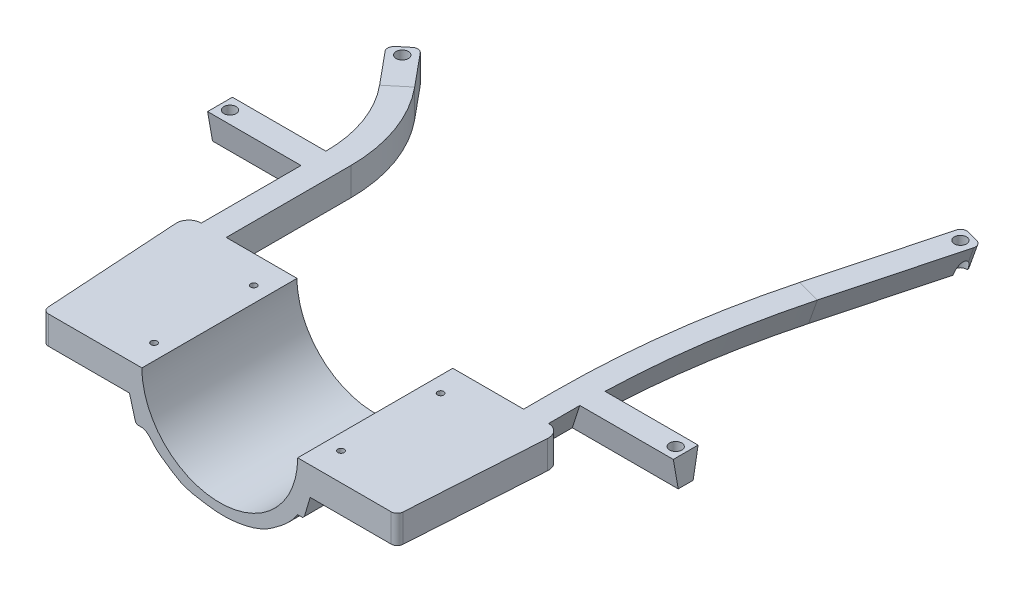
SolidWorks part; units mm, degrees
ref_plane "Front Plane" through (0, 0, 0) normal (0, 0, 1) x (1, 0, 0)
ref_plane "Top Plane" through (0, 0, 0) normal (0, 1, 0) x (1, 0, 0)
ref_plane "Right Plane" through (0, 0, 0) normal (1, 0, 0) x (0, 0, -1)
sketch "Sketch1" plane through (0, 0, 0) normal (0, 1, 0) x (1, 0, 0)
  line L1 (-38.1, 15.8115) -> (38.1, 15.8115)
  line L2 (-38.1, 15.8115) -> (-38.1, -15.8115)
  line L3 (-38.1, -15.8115) -> (38.1, -15.8115)
  line L4 (38.1, 15.8115) -> (38.1, -15.8115)
  line L5 (-38.1, 15.8115) -> (38.1, -15.8115) construction
  line L6 (-38.1, -15.8115) -> (38.1, 15.8115) construction
  point P0 (0, 0)
  dimension "D1" = 76.2
  dimension "D2" = 31.623
extrude "Boss-Extrude1" add sketch "Sketch1" along normal blind 5.715
sketch "Sketch2" plane through (0, 5.715, 0) normal (0, 1, 0) x (1, 0, 0)
  line L0 (-38.1, 15.8115) -> (-38.1, -15.8115)
  line L1 (-38.1, -15.8115) -> (-36.1, -15.8115)
  line L2 (-38.1, -15.8115) -> (38.1, -15.8115) construction
  line L3 (-36.1, -15.8115) -> (-38.1, 15.8115)
  dimension "D1" = 2
extrude "Cut-Extrude1" cut sketch "Sketch2" against normal blind 5.715
mirror "Mirror1" about plane through (0, 0, 0) normal (1, 0, 0) of "Cut-Extrude1"
fillet "Fillet1" radius 2.54 2 edges at (38.1, 2.8575, -15.8115) (-38.1, 2.8575, -15.8115)
fillet "Fillet2" radius 1.27 2 edges at (36.1, 2.8575, 15.8115) (-36.1, 2.8575, 15.8115)
sketch "Sketch3" plane through (0, 5.715, 0) normal (0, 1, 0) x (1, 0, 0)
  line L0 (-15.875, 15.8115) -> (-15.875, -15.8115) construction
  line L2 (35.3943, 15.8115) -> (-35.3943, 15.8115) construction
  line L3 (-34.9078, -15.8115) -> (34.9078, -15.8115) construction
  line L4 (-15.875, -15.8115) -> (15.875, -15.8115) construction
  line L5 (15.875, -15.8115) -> (15.875, 15.8115) construction
  line L6 (15.875, 15.8115) -> (-15.875, 15.8115) construction
  line L8 (15.875, 15.8115) -> (-15.875, 15.8115)
  line L9 (15.875, 15.8115) -> (15.875, -15.8115)
  line L10 (15.875, -15.8115) -> (-15.875, -15.8115)
  line L11 (-15.875, 15.8115) -> (-15.875, -15.8115)
  line L12 (15.875, 15.8115) -> (-15.875, -15.8115) construction
  line L13 (15.875, -15.8115) -> (-15.875, 15.8115) construction
  point P7 (0, 0)
  dimension "D1" = 31.75
  dimension "D2" = 15.875
extrude "Cut-Extrude2" cut sketch "Sketch3" against normal blind 5.715
sketch "Sketch4" plane through (0, 0, 0) normal (0, 0, 1) x (1, 0, 0)
  line L0 (-15.875, 0) -> (-18.415, 0)
  line L1 (-18.415, 0) -> (-17.0978, -4.8055)
  line L2 (17.145, -4.318) -> (15.8423, -4.318)
  line L3 (-17.0978, -4.8055) -> (-15.875, -4.8055)
  line L4 (15.875, 0) -> (18.415, 0)
  line L5 (15.875, 0) -> (34.9078, 0) construction
  line L6 (18.415, 0) -> (17.145, -4.318)
  line L9 (-15.875, 5.715) -> (-15.875, 0)
  line L10 (15.875, 5.715) -> (15.875, 0)
  ellipse E0 centre (0, 5.715) end of major axis (0, 21.59) minor radius 15.875 (-15.875, 5.715) -> (15.875, 5.715) ccw
  spline S0 degree 3 poles (15.8423, -4.318) (15.2789, -5.2246) (14.0107, -6.7523) (11.6877, -8.5827) (9.0128, -10.5096) (4.9873, -11.7991) (0.6001, -12.2924) (-3.6668, -11.6738) (-7.485, -11.0593) (-10.5564, -8.9369) (-13.429, -7.0178) (-14.6584, -4.9602) (-15.875, -4.8055) knots 0 0 0 0 0.087997 0.162006 0.243582 0.358044 0.50585 0.602946 0.713757 0.819127 0.905429 1 1 1 1
  point P0 (-15.875, 0)
  point P16 (0, -4.8055)
  point P18 (0, 5.715)
  dimension "D1" = 2.54
  dimension "D4" = 2.54
  dimension "D7" = 15.875
extrude "Boss-Extrude3" add sketch "Sketch4" along direction (0, 0, -1) on the side of the normal up to surface (15.8115 mm away) and the other way up to surface (15.8115 mm away) up to face at (-25.3914, 2.8575, 15.8115) other way up to face at (-25.6346, 2.8575, -15.8115)
chamfer "Chamfer1" distance 0.254 angle 45 2 edges at (-17.0978, -4.8055, 0) (17.145, -4.318, 0) first distance on face at (-17.7564, -2.4027, 0) first distance on face at (16.4936, -4.318, 0)
sketch "Sketch5" plane through (0, 5.715, 0) normal (0, 1, 0) x (1, 0, 0)
  circle A0 centre (-19.05, -10.16) radius 0.635
  circle A1 centre (-19.05, 10.16) radius 0.635
  circle A2 centre (19.05, 10.16) radius 0.635
  circle A3 centre (19.05, -10.16) radius 0.635
  dimension "D1" = 1.27
  dimension "D2" = 1.27
  dimension "D3" = 1.27
  dimension "D4" = 1.27
  dimension "D5" = 20.32
  dimension "D6" = 10.16
  dimension "D7" = 19.05
  dimension "D8" = 19.05
extrude "Cut-Extrude3" cut sketch "Sketch5" against normal blind 5.715
sketch "Sketch7" plane through (0, 0, -15.8115) normal (0, 0, -1) x (-1, 0, 0)
  line L0 (15.875, 5.715) -> (35.3943, 5.715) construction
  line L1 (30.3143, 5.715) -> (35.3943, 5.715)
  line L2 (30.3143, 5.715) -> (30.3143, 0)
  line L4 (18.415, 0) -> (35.3943, 0) construction
  line L7 (30.3143, 0) -> (32.8543, 0)
  line L8 (32.8543, 0) -> (35.3943, 5.715)
  line L10 (35.3943, 0) -> (35.3943, 5.715) construction
  dimension "D1" = 5.08
  dimension "D2" = 0
  dimension "D3" = 2.54
ref_plane "Plane1" through (0, 2.8575, 0) normal (0, 1, 0) x (1, 0, 0)
sketch "Sketch8" plane through (0, 2.8575, 0) normal (0, 1, 0) x (1, 0, 0)
  line L0 (-34.29, 15.8115) -> (-34.29, 41.2115)
  line L1 (-40.7142, 59.036) -> (-46.99, 66.6115)
  line L2 (34.29, 15.8115) -> (34.29, 46.0582)
  line L3 (39.9663, 89.4788) -> (40.64, 92.0115)
  line L4 (34.29, 54.1836) -> (34.4855, 54.1836)
  line L5 (35.3943, 15.8115) -> (15.875, 15.8115) construction
  line L6 (-15.875, 15.8115) -> (-35.3943, 15.8115) construction
  arc A0 (-34.29, 41.2115) -> (-40.7142, 59.036) centre (-62.23, 41.2115) ccw
  arc A1 (34.29, 46.0582) -> (39.9663, 89.4788) centre (203.2, 46.0582) cw
  dimension "D4" = 168.91
  dimension "D10" = 27.94
  dimension "D1" = 12.7
  dimension "D2" = 76.2
  dimension "D3" = 6.35
  dimension "D5" = 0
  dimension "D6" = 0
  dimension "D7" = 50.8
  dimension "D8" = 68.58
  dimension "D9" = 34.29
  dimension "D11" = 25.4
sweep "Sweep1" add profiles "Sketch7" path "Sketch8"
fillet "Fillet5" radius 1.27 2 edges at (-46.8624, 2.8575, -66.7172) (-43.9284, 2.8575, -69.1478)
sketch "Sketch9" plane through (0, 2.8575, 0) normal (0, 1, 0) x (1, 0, 0)
  line L0 (33.1857, 15.8115) -> (33.1857, 22.1863)
  line L1 (38.862, 65.6068) -> (45.8857, 92.0115)
  line L2 (33.1857, 30.3651) -> (33.3838, 30.3651)
  line L3 (-35.3943, 41.2115) -> (-35.3943, 15.8115) construction
  line L4 (35.3943, 15.8115) -> (15.875, 15.8115) construction
  arc A0 (33.1857, 22.1863) -> (38.862, 65.6068) centre (202.0957, 22.1863) cw
  dimension "D3" = 168.91
  dimension "D1" = 76.2
  dimension "D2" = 12.7
  dimension "D4" = 68.58
  dimension "D5" = 33.1857
  dimension "D6" = 0
sketch "Sketch10" plane through (0, 0, -15.8115) normal (0, 0, -1) x (-1, 0, 0)
  line L1 (-30.3143, 5.715) -> (-30.3143, 0)
  line L2 (-35.3943, 5.715) -> (-15.875, 5.715) construction
  line L3 (-35.3943, 0) -> (-18.415, 0) construction
  line L4 (-30.3143, 0) -> (-32.8543, 0)
  line L6 (-32.8543, 0) -> (-35.3943, 5.715)
  line L7 (-35.3943, 5.715) -> (-30.3143, 5.715)
  line L8 (-35.3943, 5.715) -> (-35.3943, 0) construction
  dimension "D1" = 5.08
  dimension "D2" = 2.54
  dimension "D3" = 0
sweep "Sweep2" add profiles "Sketch10" path "Sketch9"
fillet "Fillet6" radius 1.27 2 edges at (46.7927, 2.8575, -91.7702) (43.1108, 2.8575, -92.7496)
sketch "Sketch12" plane through (0, 5.715, 0) normal (0, 1, 0) x (1, 0, 0)
  line L0 (35.3943, 22.1863) -> (35.3943, 15.8115) construction
  line L1 (30.3894, 22.1863) -> (54.4443, 22.1863)
  line L2 (30.3894, 22.1863) -> (30.3894, 27.2663)
  line L3 (30.3894, 27.2663) -> (54.4443, 27.2663)
  line L4 (54.4443, 22.1863) -> (54.4443, 27.2663)
  line L5 (-35.3943, 41.2115) -> (-35.3943, 15.8115) construction
  line L6 (-30.3143, 41.2115) -> (-54.4443, 41.2115)
  line L7 (-30.3143, 41.2115) -> (-30.3143, 36.1315)
  line L8 (-30.3143, 36.1315) -> (-54.4443, 36.1315)
  line L9 (-54.4443, 41.2115) -> (-54.4443, 36.1315)
  arc A0 (36.0871, 66.345) -> (30.3143, 22.1863) centre (202.0957, 22.1863) ccw construction
  dimension "D2" = 19.05
  dimension "D1" = 5.08
  dimension "D3" = 5.08
  dimension "D4" = 19.05
extrude "Boss-Extrude5" add sketch "Sketch12" against normal blind 5.715
chamfer "Chamfer3" distance 1.016 angle 80 2 edges at (43.6493, 0, -22.1863) (43.6874, 0, -27.2663) first distance on face at (31.6739, 0, -15.8745)
chamfer "Chamfer4" distance 1.016 angle 80 2 edges at (-43.6493, 0, -36.1315) (-43.6493, 0, -41.2115) first distance on face at (-31.1417, 0, -19.5081)
sketch "Sketch13" plane through (0, 5.715, 0) normal (0, 1, 0) x (1, 0, 0)
  line L0 (-54.4443, 36.1398) -> (-35.3943, 36.1398) construction
  line L1 (-54.4443, 41.2032) -> (-54.4443, 36.1398) construction
  line L2 (-37.6526, 61.5723) -> (-43.1182, 68.1698) construction
  line L3 (-46.7701, 66.7936) -> (-44.9064, 68.3376) construction
  line L4 (40.9964, 65.0391) -> (47.6936, 90.2164) construction
  line L5 (54.4443, 22.1946) -> (54.4443, 27.258) construction
  line L6 (54.4443, 27.258) -> (35.4715, 27.258) construction
  line L7 (44.3381, 92.4232) -> (46.677, 91.801) construction
  circle A0 centre (-52.4123, 38.6798) radius 1.25
  circle A1 centre (-44.5881, 65.9626) radius 1.25
  circle A2 centre (45.0433, 90.1338) radius 1.25
  circle A3 centre (52.4123, 24.718) radius 1.25
  point P23 (45.5075, 92.1121)
  dimension "D1" = 2.5
  dimension "D3" = 2.032
  dimension "D4" = 2.5
  dimension "D5" = 2.54
  dimension "D6" = 2.032
  dimension "D7" = 2.5
  dimension "D8" = 2.032
  dimension "D9" = 2.54
  dimension "D10" = 2.5
  dimension "D12" = 2.54
  dimension "D2" = 2.54
  dimension "D11" = 2.032
extrude "Cut-Extrude4" cut sketch "Sketch13" against normal blind 8.255
